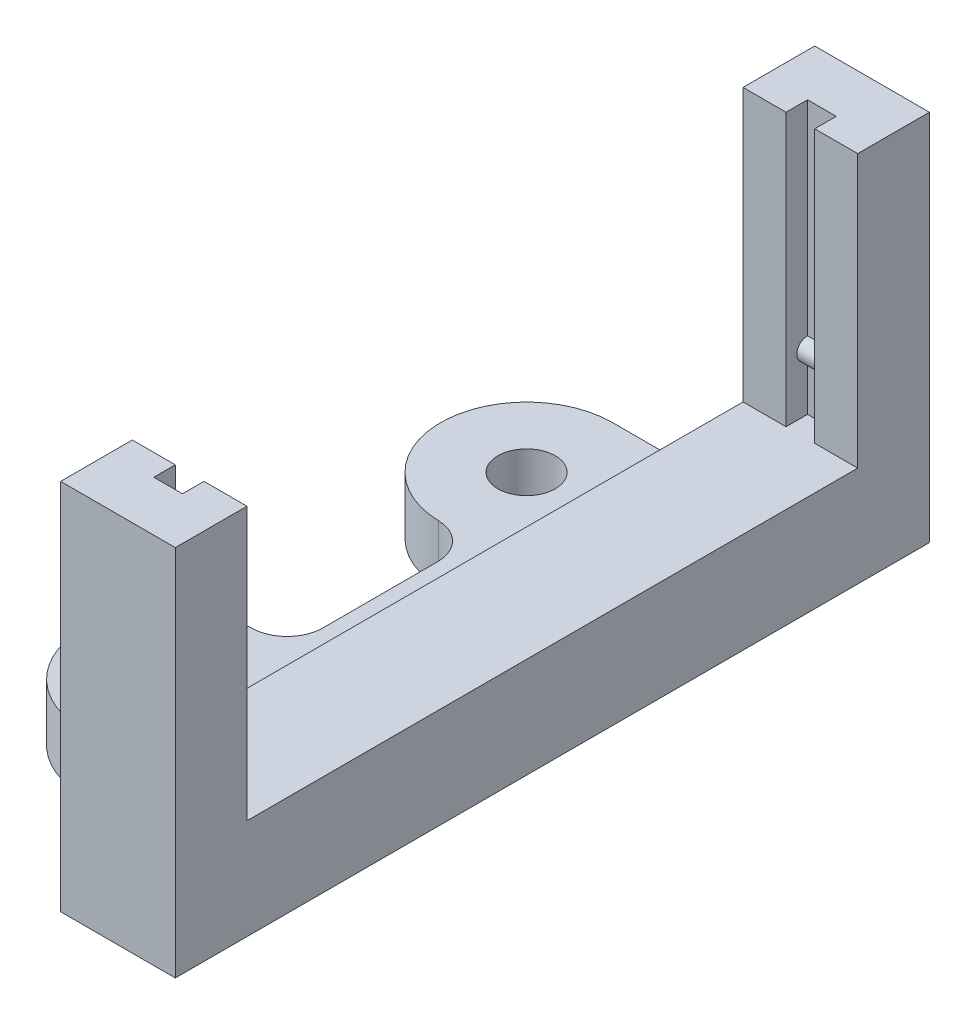
SolidWorks part; units mm, degrees
ref_plane "Front Plane" through (0, 0, 0) normal (0, 0, 1) x (1, 0, 0)
ref_plane "Top Plane" through (0, 0, 0) normal (0, 1, 0) x (1, 0, 0)
ref_plane "Right Plane" through (0, 0, 0) normal (1, 0, 0) x (0, 0, -1)
sketch "Sketch1" plane through (0, 0, 0) normal (0, 1, 0) x (1, 0, 0)
  line L0 (22.648, 0) -> (22.648, 12.5)
  line L1 (0, 0) -> (49.3027, 0)
  line L2 (0, 0) -> (0, 35.2162)
  line L3 (0, 35.2162) -> (49.3027, 35.2162)
  line L4 (49.3027, 0) -> (49.3027, 35.2162)
  line L5 (16.648, 12.5) -> (16.648, -12.5)
  line L6 (22.648, 18.5) -> (36.948, 18.5)
  line L7 (36.948, 26.3) -> (36.948, -26.3)
  line L8 (28.948, 26.3) -> (28.948, -26.3)
  line L9 (22.648, -18.5) -> (36.948, -18.5)
  line L10 (24.948, 6.5) -> (24.948, -6.5)
  line L11 (22.648, 6.5) -> (24.948, 6.5)
  line L12 (22.648, -6.5) -> (24.948, -6.5)
  line L13 (28.948, 26.3) -> (36.948, 26.3)
  line L14 (28.948, -26.3) -> (36.948, -26.3)
  circle A0 centre (22.648, 12.5) radius 2
  circle A1 centre (22.648, 12.5) radius 6
  circle A2 centre (22.648, -12.5) radius 2
  circle A3 centre (22.648, -12.5) radius 6
  point P20 (34.6513, 0)
  point P21 (30.6513, 0)
  point P25 (24.948, 0)
  dimension "D2" = 12
  dimension "D6" = 8
  dimension "D1" = 12.5
  dimension "D3" = 4
  dimension "D4" = 26.3
  dimension "D5" = 6.3
extrude "Boss-Extrude1" add sketch "Sketch1" along normal blind 4 contours A1 L11 L10 L1 L8 L6 | L12 A3 L9 L8 L1 L10 | A1 A0 | A3 A2 region at (27.2192, 0, -7.1616) region at (18.5253, 0, -8.3774) region at (27.2192, 0, 7.1616) region at (18.5253, 0, 8.3774)
extrude "Boss-Extrude2" add sketch "Sketch1<3>" along normal blind 7 contours L6 L8 L1 L7 | L8 L9 L7 L1 | L13 L8 L6 L7 | L8 L14 L7 L9 region at (32.948, 0, -9.25) region at (32.948, 0, 9.25) region at (32.948, 0, -22.4) region at (32.948, 0, 22.4)
sketch "Sketch1<3>" plane through (0, 0, 0) normal (0, 1, 0) x (1, 0, 0) same geometry as "Sketch1"
sketch "Sketch5" plane through (0, 4, 0) normal (0, 1, 0) x (1, 0, 0)
  line L0 (31.948, 22.8) -> (33.948, 22.8)
  line L1 (24.948, 6.5) -> (24.948, -6.5) construction
  line L7 (32.948, 22.8) -> (32.948, 26.3)
  line L8 (28.948, 26.3) -> (36.948, 26.3) construction
  line L9 (31.948, 22.8) -> (31.948, 21.3)
  line L10 (31.948, 21.3) -> (28.948, 21.3)
  line L11 (28.948, 21.3) -> (28.948, 26.3)
  line L12 (28.948, 26.3) -> (36.948, 26.3)
  line L13 (33.948, 22.8) -> (33.948, 21.3)
  line L14 (33.948, 21.3) -> (36.948, 21.3)
  line L15 (36.948, 21.3) -> (36.948, 26.3)
  line L16 (24.948, 0) -> (45.338, 0)
  line L17 (36.948, -21.3) -> (36.948, -26.3)
  line L18 (33.948, -21.3) -> (36.948, -21.3)
  line L19 (33.948, -22.8) -> (33.948, -21.3)
  line L20 (28.948, -26.3) -> (36.948, -26.3)
  line L21 (28.948, -21.3) -> (28.948, -26.3)
  line L22 (31.948, -21.3) -> (28.948, -21.3)
  line L23 (31.948, -22.8) -> (31.948, -21.3)
  line L24 (32.948, -22.8) -> (32.948, -26.3)
  line L25 (31.948, -22.8) -> (33.948, -22.8)
  point P4 (24.948, 0)
  point P16 (32.948, 26.3)
  point P29 (32.948, -26.3)
  dimension "D1" = 22.8
  dimension "D2" = 2
  dimension "D3" = 1.5
  dimension "D4" = 3
  dimension "D5" = 5
extrude "Boss-Extrude3" add sketch "Sketch5" along normal blind 22 contours L10 L9 L0 L7 | L13 L14 L7 L0 | L25 L24 L20 L18 L19 | L25 L23 L22 L24 region at (30.8264, 4, -23.9419) region at (35.0696, 4, -23.9419) region at (35.0696, 4, 23.9419) region at (30.8264, 4, 23.9419)
sketch "Sketch6" plane through (31.948, 0, 0) normal (1, 0, 0) x (0, 0, -1)
  line L0 (22.8, 11.75) -> (22.8, 10.25)
  line L1 (21.3, 7) -> (-21.3, 7) construction
  line L2 (22.8, 26) -> (22.8, 7) construction
  line L5 (0, 7) -> (0, 12.1575)
  line L6 (-22.8, 11.75) -> (-22.8, 10.25)
  arc A0 (22.8, 11.75) -> (22.8, 10.25) centre (22.8, 11) ccw
  arc A1 (-22.8, 11.75) -> (-22.8, 10.25) centre (-22.8, 11) cw
  line M4 (22.8, 7) -> (22.8, 26)
  dimension "D1" = 1.5
  dimension "D2" = 4
extrude "Boss-Extrude4" add sketch "Sketch6" along normal up to surface (2 mm away) contours A0 M4 | A1 L6 region at (31.948, 11, -22.4817) region at (31.948, 11, 22.4817) up to face at (33.948, 16.5, 22.05)
fillet "Fillet1" radius 2.5 4 edges at (28.948, 2, 18.5) (24.948, 2, 6.5) (24.948, 2, -6.5) (28.948, 2, -18.5)
